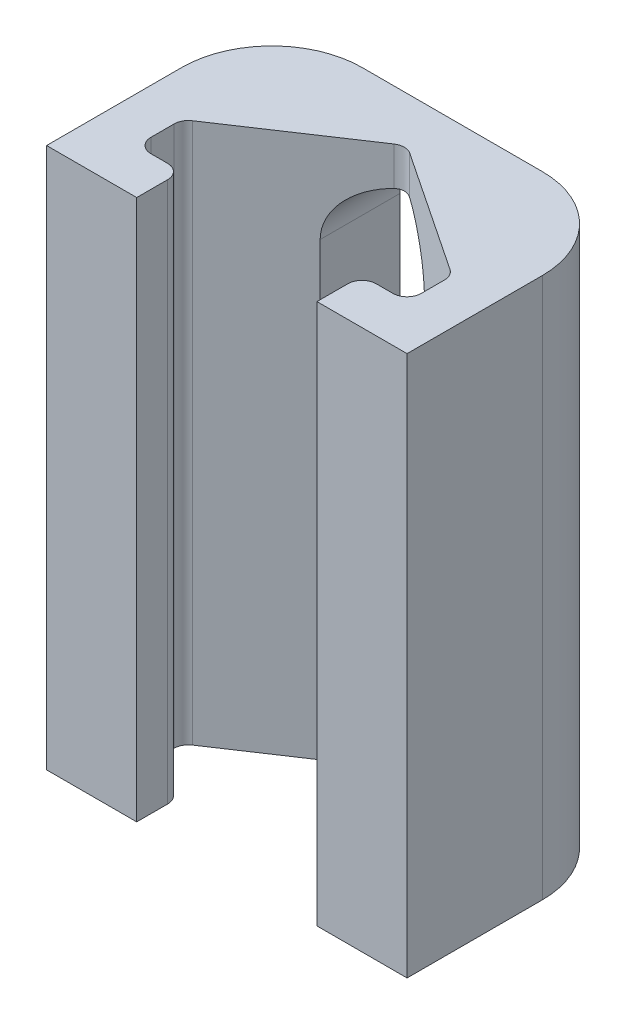
SolidWorks part; units mm, degrees
ref_plane "Front Plane" through (0, 0, 0) normal (0, 0, 1) x (1, 0, 0)
ref_plane "Top Plane" through (0, 0, 0) normal (0, 1, 0) x (1, 0, 0)
ref_plane "Right Plane" through (0, 0, 0) normal (1, 0, 0) x (0, 0, -1)
sketch "Sketch2" plane through (0, 0, 0) normal (0, 0, 1) x (1, 0, 0)
  line L0 (-71.4143, -70) -> (71.4143, -70)
  arc A0 (-71.4143, -70) -> (71.4143, -70) centre (0, 0) ccw
  point P5 (0, -70)
  point P6 (0, -100)
  dimension "D1" = 200
  dimension "D2" = 30
extrude "Boss-Extrude1" add sketch "Sketch2" along normal blind 127
sketch "Sketch3" plane through (0, 0, 0) normal (0, 1, 0) x (1, 0, 0)
  line L0 (-52.3643, -127) -> (-52.3643, -117.475)
  line L1 (71.4143, -127) -> (-71.4143, -127) construction
  line L2 (-46.0143, -111.125) -> (-33.3143, -111.125)
  line L3 (-26.9643, -117.475) -> (-26.9643, -127)
  line L4 (-26.9643, -127) -> (-33.3143, -127)
  line L5 (-33.3143, -127) -> (-33.3143, -123.825)
  line L6 (-33.3143, -123.825) -> (-30.1393, -123.825)
  line L7 (-30.1393, -123.825) -> (-30.1393, -120.65)
  line L8 (-30.1393, -120.65) -> (-39.6643, -114.3)
  line L9 (-39.6643, -114.3) -> (-49.1893, -120.65)
  line L10 (-49.1893, -120.65) -> (-49.1893, -123.825)
  line L11 (-49.1893, -123.825) -> (-46.0143, -123.825)
  line L12 (-46.0143, -123.825) -> (-46.0143, -127)
  line L13 (-46.0143, -127) -> (-52.3643, -127)
  line L14 (-71.4143, -127) -> (-71.4143, 0) construction
  arc A0 (-33.3143, -111.125) -> (-26.9643, -117.475) centre (-33.3143, -117.475) cw
  arc A1 (-52.3643, -117.475) -> (-46.0143, -111.125) centre (-46.0143, -117.475) cw
  point P6 (-5.8587, -123.6441)
  point P16 (-1.6759, -114.3491)
  point P17 (-2.7216, -114.8138)
  point P18 (-33.3143, -125.4125)
  point P19 (10.059, -124.1088)
  point P20 (-7.6015, -123.825)
  point P21 (0, 0)
  point P23 (-9.525, -121.5527)
  point P28 (0, 0)
  point P29 (-20.8674, -127)
  point P30 (-37.4371, -127)
  dimension "D8" = 6.35
  dimension "D1" = 12.7
  dimension "D2" = 25.4
  dimension "D3" = 3.175
  dimension "D4" = 3.175
  dimension "D5" = 9.525
  dimension "D6" = 3.175
  dimension "D7" = 3.175
  dimension "D9" = 19.05
extrude "Boss-Extrude2" add sketch "Sketch3" along normal blind 38.1
fillet "Fillet1" radius 1 7 edges at (-46.0143, 19.05, 123.825) (-33.3143, 19.05, 123.825) (-30.1393, 19.05, 123.825) (-30.1393, 19.05, 120.65) (-39.6643, 19.05, 114.3) (-49.1893, 19.05, 120.65) (-49.1893, 19.05, 123.825)
sketch "Sketch5" plane through (0, 0, 111.125) normal (0, 0, -1) x (-1, 0, 0)
  line L0 (39.6643, 31.75) -> (39.6643, 6.35) construction
  line L1 (43.3393, 31.75) -> (43.3393, 6.35)
  line L2 (35.9893, 31.75) -> (35.9893, 6.35)
  line L3 (33.3143, 31.75) -> (46.0143, 31.75) construction
  line L4 (33.3143, 38.1) -> (33.3143, 0) construction
  line L5 (46.0143, 38.1) -> (46.0143, 0) construction
  line L6 (33.3143, 38.1) -> (46.0143, 38.1) construction
  line L8 (33.3143, 0) -> (46.0143, 0) construction
  arc A0 (43.3393, 31.75) -> (35.9893, 31.75) centre (39.6643, 31.75) ccw
  arc A1 (35.9893, 6.35) -> (43.3393, 6.35) centre (39.6643, 6.35) ccw
  point P2 (39.6643, 19.05)
  point P7 (39.6643, -37.2129)
  point P16 (39.6643, 6.7592)
  dimension "D1" = 7.35
  dimension "D2" = 6.35
  dimension "D3" = 6.35
extrude "Cut-Extrude1" cut sketch "Sketch5" against normal through all both and the other way through all
delete or keep bodies "Body-Delete/Keep 1" type delete bodies bodies 101
